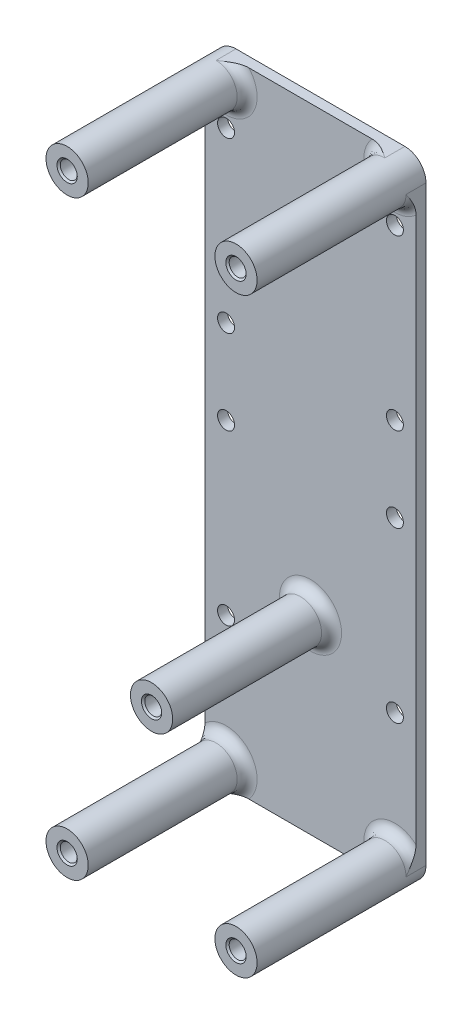
SolidWorks part; units mm, degrees
ref_plane "Front Plane" through (0, 0, 0) normal (0, 0, 1) x (1, 0, 0)
ref_plane "Top Plane" through (0, 0, 0) normal (0, 1, 0) x (1, 0, 0)
ref_plane "Right Plane" through (0, 0, 0) normal (1, 0, 0) x (0, 0, -1)
sketch "Sketch1" plane through (0, 0, 0) normal (0, 0, 1) x (1, 0, 0)
  line L1 (-25.4, 88.9) -> (25.4, 88.9) construction
  line L2 (-25.4, 88.9) -> (-25.4, -88.9) construction
  line L3 (-25.4, -88.9) -> (25.4, -88.9) construction
  line L4 (25.4, 88.9) -> (25.4, -88.9) construction
  line L5 (-25.4, 88.9) -> (25.4, -88.9) construction
  line L6 (-25.4, -88.9) -> (25.4, 88.9) construction
  line L7 (31.75, 95.25) -> (-31.75, 95.25)
  line L8 (31.75, 95.25) -> (31.75, -95.25)
  line L9 (31.75, -95.25) -> (-31.75, -95.25)
  line L10 (-31.75, 95.25) -> (-31.75, -95.25)
  line L11 (0, -95.25) -> (0, 95.25) construction
  line L12 (31.75, 0) -> (-31.75, 0) construction
  circle A0 centre (-25.4, 88.9) radius 2.5527
  circle A1 centre (25.4, 88.9) radius 2.5527
  circle A2 centre (-25.4, -88.9) radius 2.5527
  circle A3 centre (25.4, -88.9) radius 2.5527
  circle A4 centre (-25.4, 88.9) radius 6.35
  circle A5 centre (25.4, 88.9) radius 6.35
  circle A6 centre (-25.4, -88.9) radius 6.35
  circle A7 centre (25.4, -88.9) radius 6.35
  circle A8 centre (-25.4, 76.2) radius 2.5527
  circle A9 centre (25.4, 76.2) radius 2.5527
  circle A10 centre (-25.4, 0) radius 2.5527
  circle A11 centre (25.4, 0) radius 2.5527
  circle A12 centre (25.4, -50.8) radius 2.5527
  circle A13 centre (-25.4, -50.8) radius 2.5527
  circle A14 centre (0, -38.1) radius 2.5527
  circle A15 centre (0, -38.1) radius 6.35
  circle A16 centre (-25.4, 25.4) radius 2.5527
  circle A17 centre (25.4, 25.4) radius 2.5527
  point P0 (0, 0)
  point P8 (0, 0)
  point P37 (0, 0)
  dimension "D5" = 5.1054
  dimension "D6" = 5.1054
  dimension "D1" = 50.8
  dimension "D2" = 177.8
  dimension "D3" = 63.5
  dimension "D4" = 190.5
  dimension "D7" = 76.2
  dimension "D8" = 50.8
  dimension "D9" = 50.8
  dimension "D10" = 25.4
extrude "Boss-Extrude1" add sketch "Sketch1" along normal blind 3 contours A7 L8 A5 L7 A4 L10 A6 L9 A15 A13 A12 A11 A10 A9 A8 | A6 A2 | A7 A3 | A15 A14 | A4 A0 | A5 A1 region at (0, 0.2438, 0) region at (29.7631, 93.2631, 0) region at (-21.0369, 93.2631, 0) region at (29.7631, -93.2631, 0) region at (-25.4, -82.7296, 0) region at (-6.1704, -38.1, 0)
extrude "Boss-Extrude2" add sketch "Sketch1<3>" along normal blind 50.8 contours A4 A0 | A5 A1 | A15 A14 | A7 A3 | A6 A2 region at (29.7631, 93.2631, 0) region at (-21.0369, 93.2631, 0) region at (29.7631, -93.2631, 0) region at (-25.4, -82.7296, 0) region at (-6.1704, -38.1, 0)
sketch "Sketch1<3>" plane through (0, 0, 0) normal (0, 0, 1) x (1, 0, 0) same geometry as "Sketch1"
fillet "Fillet1" radius 3 5 edges at (-20.9099, -84.4099, 3) (20.9099, -84.4099, 3) (6.35, -38.1, 3) (20.9099, 84.4099, 3) (-20.9099, 84.4099, 3)
chamfer "Chamfer1" distance 0.5 angle 45 5 edges at (27.9527, -88.9, 50.8) (-22.8473, -88.9, 50.8) (2.5527, -38.1, 50.8) (27.9527, 88.9, 50.8) (-22.8473, 88.9, 50.8)
